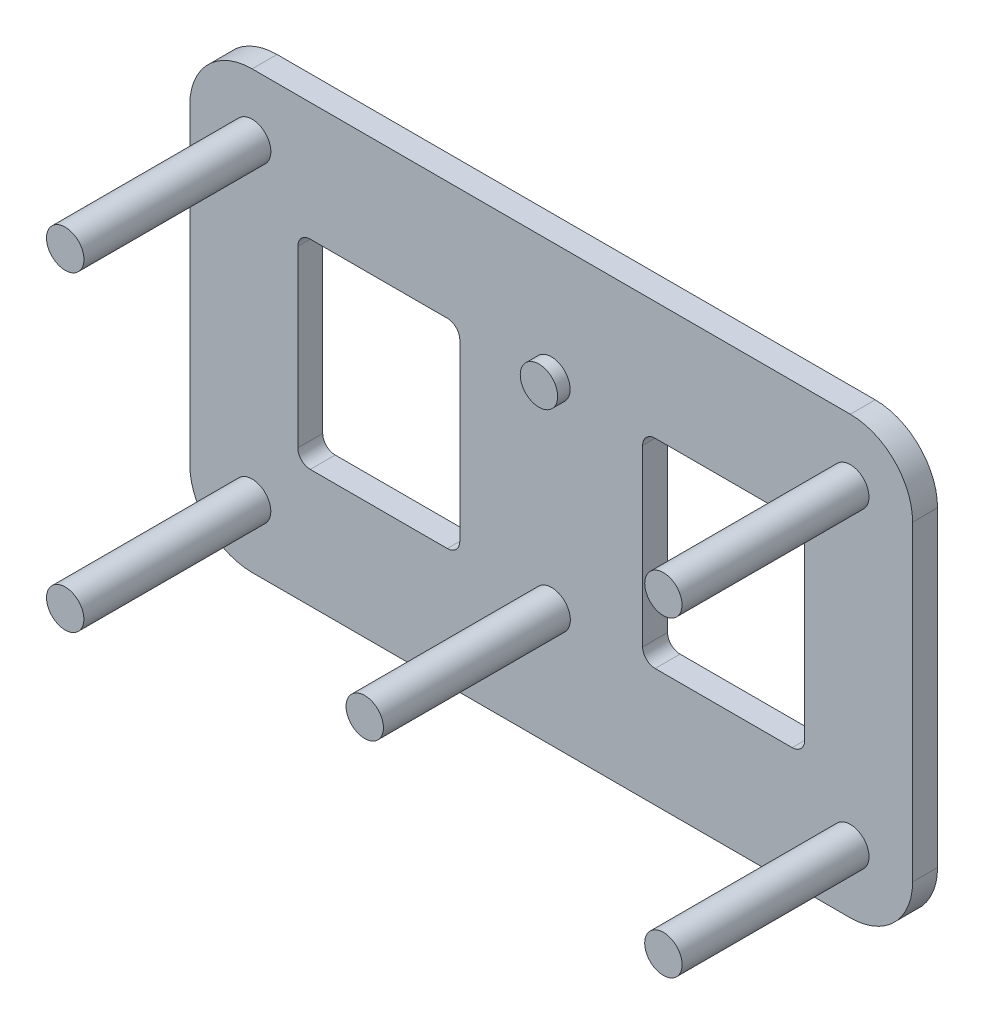
SolidWorks part; units mm, degrees
ref_plane "Ebene vorne" through (0, 0, 0) normal (0, 0, 1) x (1, 0, 0)
ref_plane "Ebene oben" through (0, 0, 0) normal (0, 1, 0) x (1, 0, 0)
ref_plane "Ebene rechts" through (0, 0, 0) normal (1, 0, 0) x (0, 0, -1)
sketch "Skizze1" plane through (0, 0, 0) normal (0, 0, 1) x (1, 0, 0)
  line L1 (0, 0) -> (58, 0)
  line L2 (0, 0) -> (0, 35)
  line L3 (0, 35) -> (58, 35)
  line L4 (58, 0) -> (58, 35)
  dimension "D1" = 58
  dimension "D2" = 35
extrude "Aufsatz-Linear austragen1" add sketch "Skizze1" along normal blind 2 contours L3 L4 L1 L2
fillet "Verrundung1" radius 5 4 edges at (58, 35, 1) (0, 0, 1) (0, 35, 1) (58, 0, 1)
ref_plane "Ebene1" through (53, 0, 0) normal (-1, 0, 0) x (0, 0, 1)
ref_plane "Ebene2" through (5, 0, 0) normal (1, 0, 0) x (0, 0, -1)
ref_plane "Ebene3" through (0, 5, 0) normal (0, 1, 0) x (1, 0, 0)
ref_plane "Ebene4" through (0, 30, 0) normal (0, -1, 0) x (-1, 0, 0)
sketch "Skizze10" plane through (0, 0, 2) normal (0, 0, 1) x (1, 0, 0)
  line L0 (53, 1.1) -> (53, -1.1) construction
  line L1 (-1.1, 30) -> (1.1, 30) construction
  circle A0 centre (53, 30) radius 1.4968
extrude "Aufsatz-Linear austragen6" add sketch "Skizze10" along normal blind 15
sketch "Skizze11" plane through (0, 0, 2) normal (0, 0, 1) x (1, 0, 0)
  line L0 (-1.1, 30) -> (1.1, 30) construction
  circle A0 centre (5, 30) radius 1.5035
extrude "Aufsatz-Linear austragen7" add sketch "Skizze11" along normal blind 15
sketch "Skizze12" plane through (0, 0, 2) normal (0, 0, 1) x (1, 0, 0)
  line L0 (1.1, 5) -> (-1.1, 5) construction
  line L1 (5, -1.1) -> (5, 1.1) construction
  circle A0 centre (5, 5) radius 1.4983
extrude "Aufsatz-Linear austragen8" add sketch "Skizze12" along normal blind 15
sketch "Skizze13" plane through (0, 0, 2) normal (0, 0, 1) x (1, 0, 0)
  line L0 (53, 1.1) -> (53, -1.1) construction
  line L1 (1.1, 5) -> (-1.1, 5) construction
  circle A0 centre (53, 5) radius 1.5005
extrude "Aufsatz-Linear austragen9" add sketch "Skizze13" along normal blind 15
ref_plane "Ebene5" through (0, 17.5, 0) normal (0, -1, 0) x (-1, 0, 0)
sketch "Skizze23" plane through (0, 0, 2) normal (0, 0, 1) x (1, 0, 0)
  line L0 (-11.3884, 17.5) -> (64.4034, 17.5) construction
  line L1 (5, 35) -> (53, 35) construction
  line L2 (5, 0) -> (53, 0) construction
  line L3 (29, 41.5601) -> (29, -4.3219) construction
  line L4 (36.3358, 25.5) -> (49.3358, 25.5)
  line L5 (36.3358, 25.5) -> (36.3358, 9.5)
  line L6 (36.3358, 9.5) -> (49.3358, 9.5)
  line L7 (49.3358, 25.5) -> (49.3358, 9.5)
  line L8 (36.3358, 25.5) -> (49.3358, 9.5) construction
  line L9 (36.3358, 9.5) -> (49.3358, 25.5) construction
  line L10 (0, 5) -> (0, 30) construction
  line L11 (58, 5) -> (58, 30) construction
  line L12 (21.6642, 9.5) -> (8.6642, 9.5)
  line L13 (8.6642, 25.5) -> (8.6642, 9.5)
  line L14 (21.6642, 25.5) -> (8.6642, 25.5)
  line L15 (21.6642, 25.5) -> (21.6642, 9.5)
  point P6 (42.8358, 17.5)
  dimension "D1" = 16
  dimension "D2" = 13
extrude "Schnitt-Linear austragen3" cut sketch "Skizze23" against normal blind 15
fillet "Verrundung4" radius 1 8 edges at (49.3358, 9.5, 1) (21.6642, 9.5, 1) (36.3358, 9.5, 1) (8.6642, 9.5, 1) (36.3358, 25.5, 1) (49.3358, 25.5, 1) (21.6642, 25.5, 1) (8.6642, 25.5, 1)
ref_axis "Achse1" through (65.188, 25.5, 2) along (-1, 0, 0)
ref_axis "Achse3" through (29, 0, 2) along (0, 1, 0)
sketch "Skizze24" plane through (0, 0, 2) normal (0, 0, 1) x (1, 0, 0)
  circle A0 centre (29.0155, 25.496) radius 1.502
extrude "Aufsatz-Linear austragen10" add sketch "Skizze24" along normal blind 1
ref_axis "Achse4" through (-9.4211, 9.5, 2) along (1, 0, 0)
sketch "Skizze26" plane through (0, 0, 2) normal (0, 0, 1) x (1, 0, 0)
  circle A0 centre (29.035, 9.4765) radius 1.4991
extrude "Aufsatz-Linear austragen11" add sketch "Skizze26" along normal blind 15
